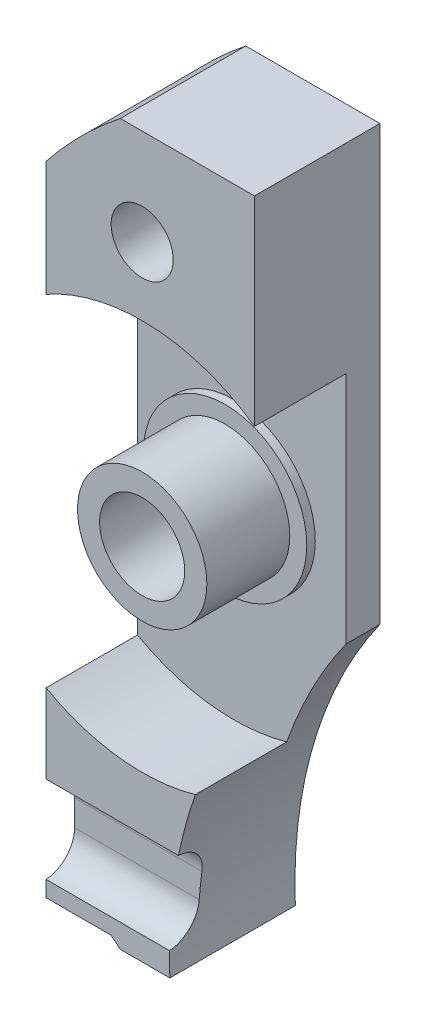
SolidWorks part; units mm, degrees
material "ABS"
ref_plane "Front Plane" through (0, 0, 0) normal (0, 0, 1) x (1, 0, 0)
ref_plane "Top Plane" through (0, 0, 0) normal (0, 1, 0) x (1, 0, 0)
ref_plane "Right Plane" through (0, 0, 0) normal (1, 0, 0) x (0, 0, -1)
sketch "Sketch1" plane through (0, 0, 0) normal (0, 0, 1) x (1, 0, 0)
  line L1 (-6.125, -21.15) -> (6.125, -21.15)
  line L2 (-6.125, -21.15) -> (-6.125, 21.15)
  line L3 (-6.125, 21.15) -> (6.125, 21.15)
  line L4 (6.125, -21.15) -> (6.125, 21.15)
  line L5 (-6.125, -21.15) -> (6.125, 21.15) construction
  line L6 (-6.125, 21.15) -> (6.125, -21.15) construction
  point P0 (0, 0)
  dimension "D1" = 12.25
  dimension "D2" = 42.3
extrude "Boss-Extrude1" add sketch "Sketch1" along normal blind 7.375
sketch "Sketch2" plane through (0, 0, 7.375) normal (0, 0, 1) x (1, 0, 0)
  line L0 (6.125, 21.15) -> (-6.125, 21.15) construction
  line L1 (-6.125, 21.15) -> (-6.125, -21.15) construction
  circle A0 centre (-0.475, 15.5) radius 1.825
  circle A1 centre (-0.475, 0) radius 2.5
  dimension "D1" = 3.65
  dimension "D2" = 5
  dimension "D3" = 5.65
  dimension "D4" = 5.65
  dimension "D5" = 15.5
extrude "Cut-Extrude1" cut sketch "Sketch2" against normal through all
sketch "Sketch3" plane through (0, 0, 7.375) normal (0, 0, 1) x (1, 0, 0)
  line L13 (-6.125, -21.15) -> (-6.125, -16.784)
  line L14 (-6.125, -21.15) -> (-1.7575, -21.15)
  line L15 (-6.125, 16.7898) -> (-6.125, 21.15)
  line L16 (-6.125, 21.15) -> (-1.7648, 21.15)
  line L17 (6.125, -4.3518) -> (6.125, -21.15)
  line L18 (6.125, -21.15) -> (1.1519, -21.15)
  arc A3 (-1.7575, -21.15) -> (-6.125, -16.784) centre (15.0221, 0.0029) cw
  arc A4 (1.1519, -21.15) -> (6.125, -4.3518) centre (28.1274, -20.0009) cw
  arc A5 (-6.125, 16.7898) -> (-1.7648, 21.15) centre (15.0221, 0.0029) cw
  dimension "D1" = 27
  dimension "D2" = 27
  dimension "D3" = 16.7982
  dimension "D4" = 4.9731
  dimension "D5" = 4.3675
  dimension "D6" = 27
  dimension "D7" = 4.366
  dimension "D8" = 4.3602
  dimension "D9" = 4.3602
extrude "Cut-Extrude2" cut sketch "Sketch3" against normal through all
sketch "Sketch4" plane through (0, 0, 7.375) normal (0, 0, 1) x (1, 0, 0)
  circle A0 centre (-0.475, 0) radius 11.5
  dimension "D1" = 23
extrude "Cut-Extrude3" cut sketch "Sketch4" against normal blind 5.375
sketch "Sketch5" plane through (0, 0, 2) normal (0, 0, 1) x (1, 0, 0)
  circle A0 centre (-0.475, 0) radius 4.8
  circle A1 centre (-0.475, 0) radius 2.5 construction
  circle A2 centre (-0.475, 0) radius 2.5
  dimension "D1" = 9.6
extrude "Boss-Extrude2" add sketch "Sketch5" along normal blind 0.5
sketch "Sketch6" plane through (0, 0, 2.5) normal (0, 0, 1) x (1, 0, 0)
  circle A0 centre (-0.475, 0) radius 3.8
  circle A1 centre (-0.475, 0) radius 2.5 construction
  circle A2 centre (-0.475, 0) radius 2.5
  dimension "D1" = 7.6
extrude "Boss-Extrude3" add sketch "Sketch6" along normal blind 4.875
sketch "Sketch7" plane through (-6.125, 0, 0) normal (1, 0, 0) x (0, 0, -1)
  line L0 (0, -4.3518) -> (0, 21.15) construction
  line L2 (-7.375, -13.7212) -> (-7.375, -20.6988)
  line L5 (-7.375, 21.15) -> (-7.375, 9.4175) construction
  line L6 (-7.375, -10.0164) -> (-2, -10.0164) construction
  arc A0 (-7.375, -20.6988) -> (-7.375, -13.7212) centre (-6, -17.21) ccw
  dimension "D1" = 7.5
  dimension "D2" = 6
  dimension "D3" = 7.1936
extrude "Boss-Extrude4" add sketch "Sketch7" along normal up to next
sketch "Sketch8" plane through (-6.125, 0, 0) normal (1, 0, 0) x (0, 0, -1)
  line L0 (-7.5, -17.9736) -> (-7.5, -16.4595) construction
  line L1 (-9.3, -17.9736) -> (-9.3, -16.4595)
  line L2 (-5.7, -17.9736) -> (-5.7, -16.4595)
  line L3 (0, -4.3518) -> (0, 21.15) construction
  line L5 (-7.375, -10.0164) -> (-2, -10.0164) construction
  arc A0 (-9.3, -17.9736) -> (-5.7, -17.9736) centre (-7.5, -17.9736) ccw
  arc A1 (-5.7, -16.4595) -> (-9.3, -16.4595) centre (-7.5, -16.4595) ccw
  point P2 (-7.5, -17.2165)
  dimension "D4" = 6.4431
  dimension "D1" = 3.6
  dimension "D2" = 7.5
  dimension "D3" = 1.5141
extrude "Cut-Extrude4" cut sketch "Sketch8" along normal through all
sketch "Sketch9" plane through (0, 0, 0) normal (0, 0, -1) x (-1, 0, 0)
  circle A0 centre (0.475, 15.5) radius 3.2
  dimension "D1" = 6.4
extrude "Cut-Extrude5" cut sketch "Sketch9" against normal blind 4
